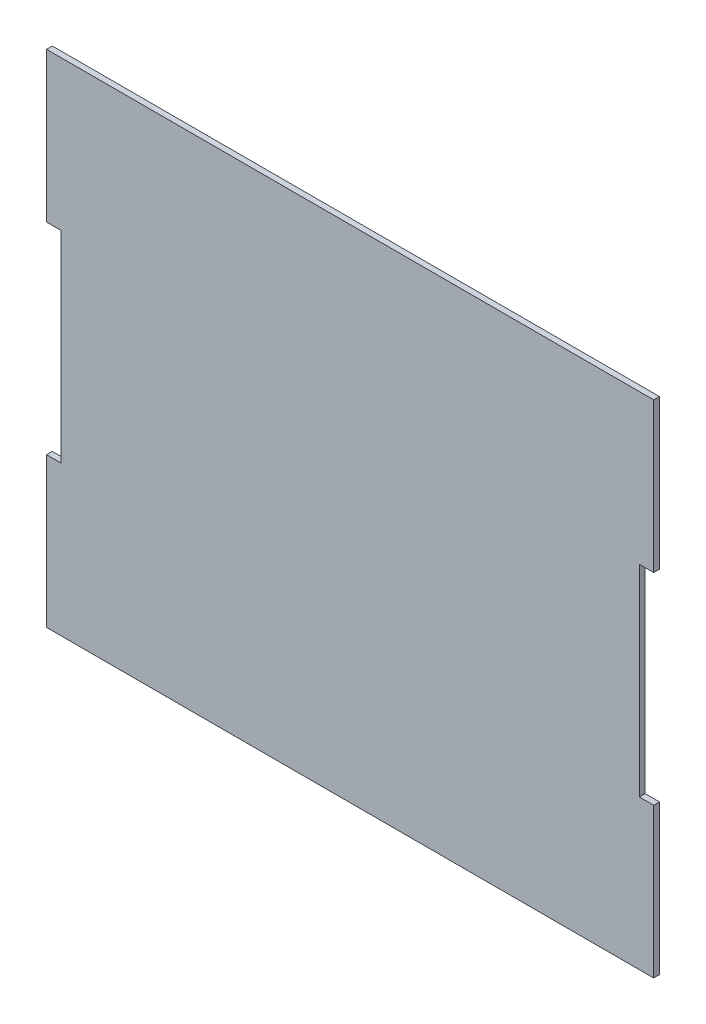
SolidWorks part; units mm, degrees
ref_plane "前视基准面" through (0, 0, 0) normal (0, 0, 1) x (1, 0, 0)
ref_plane "上视基准面" through (0, 0, 0) normal (0, 1, 0) x (1, 0, 0)
ref_plane "右视基准面" through (0, 0, 0) normal (1, 0, 0) x (0, 0, -1)
sketch "草图1" plane through (0, 0, 0) normal (0, 0, 1) x (1, 0, 0)
  line L48 (105.5, 35) -> (105.5, 87)
  line L49 (105.5, 87) -> (-105.5, 87)
  line L54 (-105.5, 35) -> (-105.5, 87)
  line L55 (-105.5, -35) -> (-105.5, -87)
  line L57 (105.5, -87) -> (-105.5, -87)
  line L58 (105.5, -35) -> (105.5, -87)
  line L60 (105.5, 35) -> (100.5, 35)
  line L61 (100.5, 35) -> (100.5, -35)
  line L62 (100.5, -35) -> (105.5, -35)
  line L63 (-105.5, 35) -> (-100.5, 35)
  line L64 (-100.5, 35) -> (-100.5, -35)
  line L65 (-100.5, -35) -> (-105.5, -35)
extrude "凸台-拉伸1" add sketch "草图1" along normal blind 2
